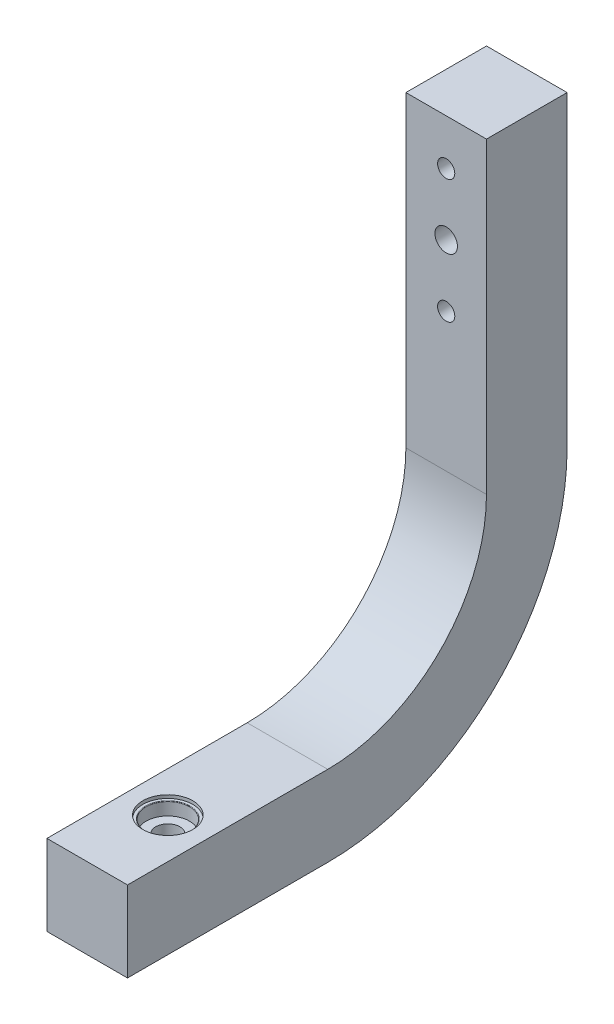
SolidWorks part; units mm, degrees
ref_plane "Front Plane" through (0, 0, 0) normal (0, 0, 1) x (1, 0, 0)
ref_plane "Top Plane" through (0, 0, 0) normal (0, 1, 0) x (1, 0, 0)
ref_plane "Right Plane" through (0, 0, 0) normal (1, 0, 0) x (0, 0, -1)
ref_axis "Z" through (0, 0, 86.1) along (0, 0, -1)
sketch "Sketch1" plane through (0, 0, 0) normal (1, 0, 0) x (0, 0, -1)
  line L0 (-15, 20) -> (0, 20)
  line L1 (0, 20) -> (0, -37.2682)
  line L2 (0, -32) -> (-49.8046, -81.8046) construction
  line L3 (-44.5364, -81.8046) -> (-66.8046, -81.8046)
  line L4 (-66.8046, -81.8046) -> (-66.8046, -66.8046) construction
  line L5 (-66.8046, -66.8046) -> (-44.5364, -66.8046)
  line L6 (-56.0178, -66.8046) -> (-15, -25.7868) construction
  line L7 (-15, -37.2682) -> (-15, 20)
  line L8 (-35.5089, -46.2957) -> (-24.9023, -56.9023) construction
  line L9 (-44.5364, -66.8046) -> (-56.0178, -66.8046) construction
  line L10 (-66.8046, -66.8046) -> (-81.8046, -66.8046)
  line L11 (-66.8046, -66.8046) -> (-66.8046, -81.8046) construction
  line L12 (-66.8046, -81.8046) -> (-81.8046, -81.8046)
  line L13 (-81.8046, -66.8046) -> (-81.8046, -81.8046)
  line L14 (-15, -25.7868) -> (-15, -37.2682) construction
  line L15 (0, -37.2682) -> (0, -32) construction
  line L16 (-49.8046, -81.8046) -> (-44.5364, -81.8046) construction
  arc A0 (-44.5364, -66.8046) -> (-15, -37.2682) centre (-44.5364, -37.2682) ccw
  arc A1 (-44.5364, -81.8046) -> (0, -37.2682) centre (-44.5364, -37.2682) ccw
  dimension "D1" = 15
  dimension "D2" = 66.8046
  dimension "D3" = 81.8046
  dimension "D4" = 20
  dimension "D5" = 135
  dimension "D6" = 49.8046
  dimension "D7" = 15
  dimension "D8" = 22.2682
extrude "Boss-Extrude1" add sketch "Sketch1" along normal blind 7.5 and the other way blind 7.5
sketch "Sketch3" plane through (0, -66.8046, 0) normal (0, 1, 0) x (1, 0, 0)
  line L0 (-8.25, 0) -> (8.25, 0) construction
  line L1 (0, -45.1) -> (0, 45.1) construction
  circle A0 centre (0, -66.8046) radius 2.25
  dimension "D2" = 4.5
  dimension "D1" = 66.8046
extrude "Cut-Extrude1" cut sketch "Sketch3" against normal through all
sketch "Sketch4" plane through (0, 0, 15) normal (0, 0, 1) x (1, 0, 0)
  line L0 (0, -11.5) -> (0, 11.5) construction
  circle A0 centre (0, 0) radius 2.1
  circle A1 centre (0, 11.5) radius 1.6
  circle A2 centre (0, -11.5) radius 1.6
  dimension "D1" = 4.2
  dimension "D3" = 3.2
  dimension "D2" = 23
extrude "Cut-Extrude2" cut sketch "Sketch4" against normal through all both and the other way through all
ref_axis "Axis1" through (0, -52.1687, 66.8046) along (0, 1, 0)
sketch "Sketch5" plane through (0, 0, 0) normal (1, 0, 0) x (0, 0, -1)
  line L0 (-62.7546, -78.8046) -> (-62.7546, -81.1046)
  line L1 (-62.6546, -81.2046) -> (-62.1546, -81.2046)
  line L2 (-62.1546, -81.2046) -> (-62.1546, -81.8046)
  line L3 (-62.1546, -81.8046) -> (-66.8046, -81.8046)
  line L4 (-66.8046, -81.8046) -> (-66.8046, -78.8046)
  line L5 (-66.8046, -78.8046) -> (-62.7546, -78.8046)
  line L6 (-66.8046, -74.3046) -> (-66.8046, -90.6731) construction
  line L7 (-66.8046, -74.3046) -> (-81.8046, -74.3046) construction
  line L8 (-66.8046, -69.8046) -> (-62.7546, -69.8046)
  line L9 (-66.8046, -66.8046) -> (-66.8046, -69.8046)
  line L10 (-62.1546, -66.8046) -> (-66.8046, -66.8046)
  line L11 (-62.1546, -67.4046) -> (-62.1546, -66.8046)
  line L12 (-62.6546, -67.4046) -> (-62.1546, -67.4046)
  line L13 (-62.7546, -69.8046) -> (-62.7546, -67.5046)
  line L16 (-66.8046, -52.1687) -> (-66.8046, -36.5447) construction
  line L17 (-81.8046, -66.8046) -> (-81.8046, -81.8046) construction
  line L18 (-66.8046, -66.8046) -> (-44.5364, -66.8046) construction
  arc A0 (-62.7546, -67.5046) -> (-62.6546, -67.4046) centre (-62.6546, -67.5046) cw
  arc A1 (-62.6546, -81.2046) -> (-62.7546, -81.1046) centre (-62.6546, -81.1046) cw
  point P23 (-62.7546, -67.4046)
  point P26 (-62.7546, -81.2046)
  dimension "D5" = 0.1
  dimension "D6" = 0.1
  dimension "D2" = 4.65
  dimension "D3" = 3
  dimension "D4" = 8.1
revolve "Cut-Revolve1" cut sketch "Sketch5" angle 360 about axis through (0, -52.1687, 66.8046) along (0, 1, 0)
equation "\"rbracket-width\"= \"L2Thickness\""
equation "\"D1@Boss-Extrude1\"=\"rbracket-width\"/2"
equation "\"D2@Boss-Extrude1\"=\"rbracket-width\"/2"
equation "\"EyeCaptureRadius\"= ( \"EyeDiameter\" + \"EyeClearance\" ) / 2"
equation "\"rbracket_planetocenterline_dist\"= \"BasePlaneDistance\""
equation "\"D2@Sketch1\"=\"rbracket_planetocenterline_dist\""
equation "\"EyeDiameter\" = 99.60916292"
equation "\"BasePlaneDistance\" = \"EyeDiameter\"/2+\"L2Thickness\"+\"EyeClearance\""
equation "\"EyeClearance\" = 2"
equation "\"D1@Sketch1\"=\"rbracket-width\""
equation "\"D3@Sketch1\"=(\"EyeDiameter\"+\"EyeClearance\"+\"EyeClearance\")/2 + \"L2Thickness\" + \"rbracket-width\""
equation "\"D6@Sketch1\"=\"EyeDiameter\"/2"
equation "\"D7@Sketch1\"=\"rbracket-width\""
equation "\"D1@Sketch3\"=\"BasePlaneDistance\""
equation "\"L2Thickness\" = 3.75 * \"shaft_diameter\""
equation "\"D8@Sketch1\"=\"rbracket_planetocenterline_dist\"/3"
equation "\"BearingFlangeOD\"= 7.5"
equation "\"BearingFlangeThickness\"= 0.75"
equation "\"BearingHousingID\"=4.5"
equation "\"BearingDepth\"= 6"
equation "\"PrinterFilamentThickness\"= 0.1"
equation "\"ApplyPrinterOffsets\"= 1"
equation "\"L2_ID\" = 20"
equation "\"vx\" = 50"
equation "\"vy\" = 10"
equation "\"vz\" = 100"
equation "\"parametric_end\" = 1"
equation "\"Rw_3_xx\" = -(\"vz\")/sqr((\"vx\")^2 + (\"vz\")^2)"
equation "\"Rw_3_xy\" = 0"
equation "\"Rw_3_xz\" = (\"vx\")/sqr((\"vx\")^2 + (\"vz\")^2)"
equation "\"Rw_3_zx\" = (\"vx\")/sqr((\"vx\")^2 + (\"vy\")^2 + (\"vz\")^2)"
equation "\"Rw_3_zy\" = (\"vy\")/sqr((\"vx\")^2 + (\"vy\")^2 + (\"vz\")^2)"
equation "\"Rw_3_zz\" = (\"vz\")/sqr((\"vx\")^2 + (\"vy\")^2 + (\"vz\")^2)"
equation "\"Rw_3_yx\" = (\"vx\")*(\"vy\")/sqr((\"vx\")^4 + (\"vx\")^2*(\"vy\")^2 + 2*(\"vx\")^2*(\"vz\")^2 + (\"vy\")^2*(\"vz\")^2 + (\"vz\")^4)"
equation "\"Rw_3_yy\" = -sqr((\"vx\")^2 + (\"vz\")^2)/sqr((\"vx\")^2 + (\"vy\")^2 + (\"vz\")^2)"
equation "\"Rw_3_yz\" = (\"vy\")*(\"vz\")/sqr((\"vx\")^4 + (\"vx\")^2*(\"vy\")^2 + 2*(\"vx\")^2*(\"vz\")^2 + (\"vy\")^2*(\"vz\")^2 + (\"vz\")^4)"
equation "\"O2Targx\" = -\"BasePlaneDistance\"*(\"vx\")*(\"vy\")/sqr((\"vx\")^4 + (\"vx\")^2*(\"vy\")^2 + 2*(\"vx\")^2*(\"vz\")^2 + (\"vy\")^2*(\"vz\")^2 + (\"vz\")^4)"
equation "\"O2Targy\" = \"BasePlaneDistance\"*sqr((\"vx\")^2 + (\"vz\")^2)/sqr((\"vx\")^2 + (\"vy\")^2 + (\"vz\")^2)"
equation "\"O2Targz\" = -\"BasePlaneDistance\"*(\"vy\")*(\"vz\")/sqr((\"vx\")^4 + (\"vx\")^2*(\"vy\")^2 + 2*(\"vx\")^2*(\"vz\")^2 + (\"vy\")^2*(\"vz\")^2 + (\"vz\")^4)"
equation "\"O2Targx_0\" = -(\"BasePlaneDistance\")*sqr((\"vx\")^2 + (\"vz\")^2)/sqr((\"vx\")^2 + (\"vy\")^2 + (\"vz\")^2)"
equation "\"O2Targy_0\" = -(\"BasePlaneDistance\")*(\"vy\")*(\"vz\")/sqr((\"vx\")^4 + (\"vx\")^2*(\"vy\")^2 + 2*(\"vx\")^2*(\"vz\")^2 + (\"vy\")^2*(\"vz\")^2 + (\"vz\")^4)"
equation "\"O2Targz_0\" = (\"BasePlaneDistance\")*(\"vx\")*(\"vy\")/sqr((\"vx\")^4 + (\"vx\")^2*(\"vy\")^2 + 2*(\"vx\")^2*(\"vz\")^2 + (\"vy\")^2*(\"vz\")^2 + (\"vz\")^4) + (\"BasePlaneDistance\")"
equation "\"theta2_s1\" = arcsin(((\"BasePlaneDistance\") - (\"O2Targz_0\"))/(\"BasePlaneDistance\")) + pi"
equation "\"theta2_s2\" = -arcsin(((\"BasePlaneDistance\") - (\"O2Targz_0\"))/(\"BasePlaneDistance\"))"
equation "\"theta1_s1\" = arcsin((\"O2Targy_0\")/((\"BasePlaneDistance\")*cos((\"Theta2\")))) + pi"
equation "\"theta1_s2\" = -arcsin((\"O2Targy_0\")/((\"BasePlaneDistance\")*cos((\"Theta2\"))))"
equation "\"theta1_s3\" = -arccos(-(\"O2Targx_0\")/((\"BasePlaneDistance\")*cos((\"Theta2\")))) + 2*pi"
equation "\"theta1_s4\" = arccos(-(\"O2Targx_0\")/((\"BasePlaneDistance\")*cos((\"Theta2\"))))"
equation "\"Theta1\" = \"theta1_s2\" 'so far, theta1_s1 and theta1_s4 have agreed, and they agree with the sw constraint solver"
equation "\"Theta2\" = \"theta2_s2\""
equation "\"o2_x\" = -(\"BasePlaneDistance\")*cos((\"Theta1\"))*cos((\"Theta2\"))"
equation "\"o2_y\" = -(\"BasePlaneDistance\")*sin((\"Theta1\"))*cos((\"Theta2\"))"
equation "\"o2_z\" = (\"BasePlaneDistance\")*(sin((\"Theta2\")) + 1)"
equation "\"o1_x\" = (\"BasePlaneDistance\")*sin((\"Theta1\"))"
equation "\"o1_y\" = -(\"BasePlaneDistance\")*cos((\"Theta1\"))"
equation "\"o1_z\" = (\"BasePlaneDistance\")"
equation "\"Actuator1_Theta\" = atn(\"vx\"/\"vz\") 'ik solution for the single link joint"
equation "\"Actuator2_Theta\" = \"Theta1\"  'ik solution for the double link joint"
equation "\"MotorBaseThickness\" = 3 "
equation "\"BaseThickness\" = 3 "
equation "\"EncoderToMagnetAirgap\" = 1 'Encoder to magnet airgap"
equation "\"EncoderHeight\" = 1.192  'Height of the encoder"
equation "\"MagnetThickness\" = 0.5  'Magnet thickness"
equation "\"pcb_thickness\" = 1.6  'Thickness of the PCB"
equation "\"pcb_outer_diameter\" = 32 'the OD of the pcb"
equation "\"shaft_diameter\" = 4"
equation "\"D2@Sketch3\"=\"shaft_diameter\"*1.125"
equation "\"D2@Sketch5\"=\"ApplyPrinterOffsets\"*\"PrinterFilamentThickness\"/2+4.6"
equation "\"D4@Sketch5\"=\"ApplyPrinterOffsets\"*\"PrinterFilamentThickness\"+8"
